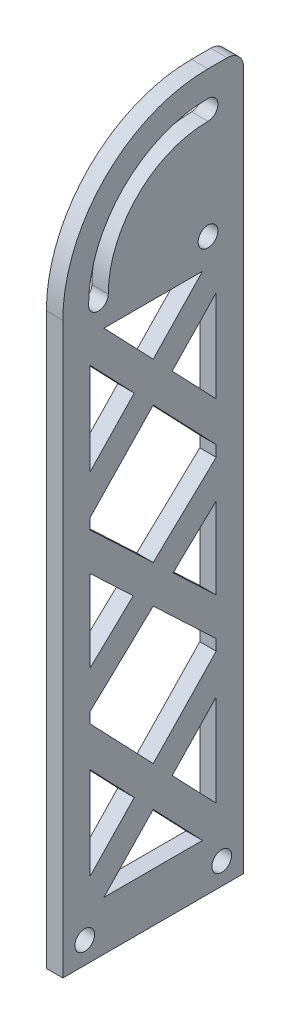
SolidWorks part; units mm, degrees
ref_plane "Front Plane" through (0, 0, 0) normal (0, 0, 1) x (1, 0, 0)
ref_plane "Top Plane" through (0, 0, 0) normal (0, 1, 0) x (1, 0, 0)
ref_plane "Right Plane" through (0, 0, 0) normal (1, 0, 0) x (0, 0, -1)
sketch "Sketch1" plane through (0, 0, 0) normal (1, 0, 0) x (0, 0, -1)
  line L0 (28, 103.9687) -> (33, 103.9687) construction
  line L1 (-14.1357, 103.9687) -> (0, 103.9687) construction
  line L2 (33, 103.9687) -> (33, 127.4687)
  line L3 (30, 130.4687) -> (26.5, 130.4687)
  line L4 (4, 4) -> (29, 4) construction
  line L5 (16.5, 4) -> (16.5, 0) construction
  line L7 (33, 103.9687) -> (33, 0)
  line L8 (33, 0) -> (0, 0)
  line L9 (0, 103.9687) -> (0, 0)
  circle A0 centre (4, 4) radius 1.5
  circle A1 centre (29, 4) radius 1.5
  circle A2 centre (26.5, 103.9687) radius 1.5
  arc A7 (0, 103.9687) -> (26.5, 130.4687) centre (26.5, 103.9687) cw
  arc A8 (33, 127.4687) -> (30, 130.4687) centre (30, 127.4687) ccw
  arc A9 (4.7, 103.9687) -> (26.5, 125.7687) centre (26.5, 103.9687) cw
  arc A10 (8.3, 103.9687) -> (26.5, 122.1687) centre (26.5, 103.9687) cw
  arc A11 (4.7, 103.9687) -> (8.3, 103.9687) centre (6.5, 103.9687) ccw
  arc A12 (26.5, 122.1687) -> (26.5, 125.7687) centre (26.5, 123.9687) ccw
  arc A13 (4.7, 103.9687) -> (26.5, 125.7687) centre (26.5, 103.9687) cw construction
  dimension "D1" = 3
  dimension "D2" = 3
  dimension "D4" = 3
  dimension "D6" = 4
  dimension "D12" = 3
  dimension "D9" = 3.6
  dimension "D11" = 20
  dimension "D3" = 4
  dimension "D5" = 100
  dimension "D10" = 5
  dimension "D15" = 33
extrude "Boss-Extrude1" add sketch "Sketch1" along normal blind 3
hole_wizard "M3 Clearance Hole1" positions "Sketch2" profile "Sketch3" hole size "M3" standard "ANSI Metric" end condition through all
sketch "Sketch2" plane through (0, 0, 0) normal (-1, 0, 0) x (0, 0, 1)
  point P0 (-29, 4)
  point P3 (-4, 4)
  point P6 (-26.5, 103.9687)
sketch "Sketch3" plane through (0, 4, -29) normal (0, 1, 0) x (0, 0, 1)
  line L0 (0, 0) -> (0, 3)
  line L1 (0, 3) -> (1.8, 3)
  line L2 (1.8, 3) -> (1.8, 0)
  line L5 (1.8, 0) -> (0, 0)
  line L11 (0, -6.35) -> (0, 107.95) construction
  dimension "Thru Hole Dia." = 3.6
  dimension "Thru Hole Depth" = 3
sketch "Sketch4" plane through (3, 0, 0) normal (1, 0, 0) x (0, 0, -1)
  line L6 (25.5, 9) -> (5, 30.4241)
  line L7 (0, 103.9687) -> (0, 0) construction
  line L8 (28, 13.6195) -> (5, 37.6562)
  line L39 (5, 98.9687) -> (28, 98.9687)
  line L40 (5, 98.9687) -> (5, 9)
  line L41 (5, 9) -> (28, 9)
  line L42 (28, 98.9687) -> (28, 9)
  line L43 (33, 0) -> (33, 127.4687) construction
  line L44 (7.5, 9) -> (28, 30.4241)
  line L45 (5, 13.6195) -> (28, 37.6562)
  line L46 (16.5, 25.6379) -> (20.1126, 22.1811) construction
  line L47 (12.8874, 22.1811) -> (16.5, 25.6379) construction
  line L48 (5, 39.6562) -> (28, 61.4277)
  line L49 (5, 46.5411) -> (28, 68.3125)
  line L50 (28, 39.6562) -> (5, 61.4277)
  line L51 (28, 46.5411) -> (5, 68.3125)
  line L52 (13.0628, 53.7956) -> (16.5, 57.4268) construction
  line L53 (19.9372, 53.7956) -> (16.5, 57.4268) construction
  line L54 (5, 39.6562) -> (28, 39.6562) construction
  line L55 (5, 37.6562) -> (28, 37.6562) construction
  line L56 (16.5, 37.6562) -> (16.5, 39.6562) construction
  line L57 (5, 70.3125) -> (28, 94.3492)
  line L58 (5, 77.5447) -> (25.5, 98.9687)
  line L59 (15.25, 88.2567) -> (18.8626, 84.7999) construction
  line L60 (28, 70.3125) -> (5, 94.3492)
  line L61 (28, 77.5447) -> (7.5, 98.9687)
  line L62 (17.75, 88.2567) -> (14.1374, 84.7999) construction
  line L63 (5, 70.3125) -> (28, 70.3125) construction
  line L64 (28, 68.3125) -> (5, 68.3125) construction
  line L65 (16.5, 70.3125) -> (16.5, 68.3125) construction
  line L66 (16.5, 98.9687) -> (16.5, 70.3125) construction
  line L67 (16.5, 68.3125) -> (16.5, 39.6562) construction
  line L68 (16.5, 37.6562) -> (16.5, 9) construction
  circle A4 centre (26.5, 103.9687) radius 1.8 construction
  circle A5 centre (29, 4) radius 1.8 construction
  circle A6 centre (4, 4) radius 1.8 construction
  circle A7 centre (26.5, 103.9687) radius 1.8 construction
  circle A8 centre (29, 4) radius 1.8 construction
  circle A9 centre (4, 4) radius 1.8 construction
  point P40 (16.5, 57.4268)
  point P43 (16.5, 57.4268)
  dimension "D1" = 5
  dimension "D2" = 5
  dimension "D3" = 5
  dimension "D4" = 5
  dimension "D5" = 5
  dimension "D6" = 2.5
  dimension "D7" = 2.5
  dimension "D8" = 2
extrude "Cut-Extrude1" cut sketch "Sketch4" against normal blind 10 contours L40 L45 L6 | L44 L41 L6 | L44 L8 L42 | L42 L50 L48 L40 L8 L45 | L51 L42 L48 | L49 L50 L40 | L42 L60 L57 L40 L51 L49 | L61 L42 L57 | L58 L60 L40 | L61 L58 L39 region at (3, 12.1352, -16.5) region at (3, 22.0218, -7.68) region at (3, 22.0218, -25.32) region at (3, 38.2927, -16.5) region at (3, 53.9844, -7.6211) region at (3, 53.9844, -25.3789) region at (3, 69.676, -16.5) region at (3, 85.947, -7.68) region at (3, 85.947, -25.32) region at (3, 95.8335, -16.5)
